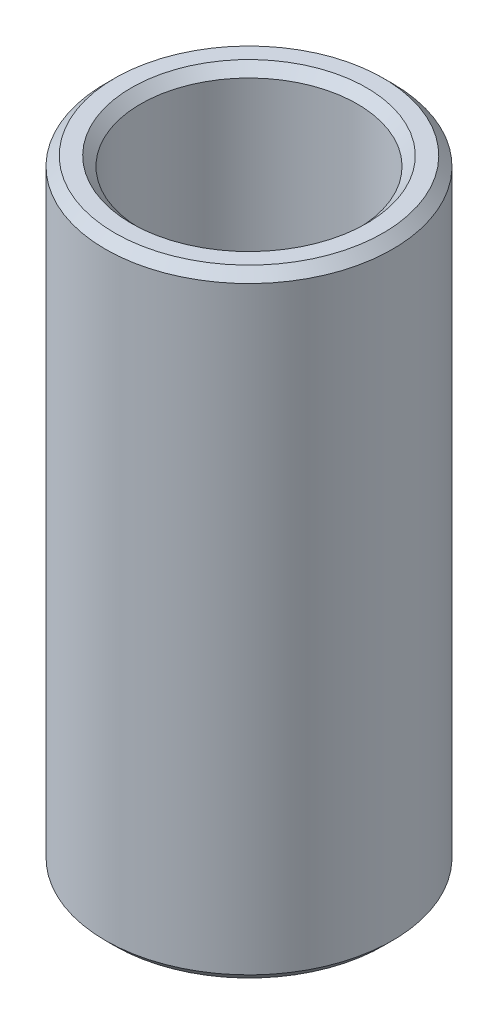
SolidWorks part; units mm, degrees
ref_plane "Front Plane" through (0, 0, 0) normal (0, 0, 1) x (1, 0, 0)
ref_plane "Top Plane" through (0, 0, 0) normal (0, 1, 0) x (1, 0, 0)
ref_plane "Right Plane" through (0, 0, 0) normal (1, 0, 0) x (0, 0, -1)
sketch "Sketch1" plane through (0, 0, 0) normal (0, 1, 0) x (1, 0, 0)
  circle A0 centre (0, 0) radius 50
  dimension "SLEEVE_OD" = 100
extrude "Boss-Extrude1" add sketch "Sketch1" along normal blind 215.0453
sketch "Sketch2" plane through (0, 0, 0) normal (0, 1, 0) x (1, 0, 0)
  circle A0 centre (0, 0) radius 37.7045
  dimension "BORE_D" = 75.409
extrude "Cut-Extrude1" cut sketch "Sketch2" along normal through all
chamfer "Chamfer1" distance 3.2587 angle 45 4 edges at (0, 215.0453, 37.7045) (0, 0, 37.7045) (0, 0, 50) (0, 215.0453, 50)
